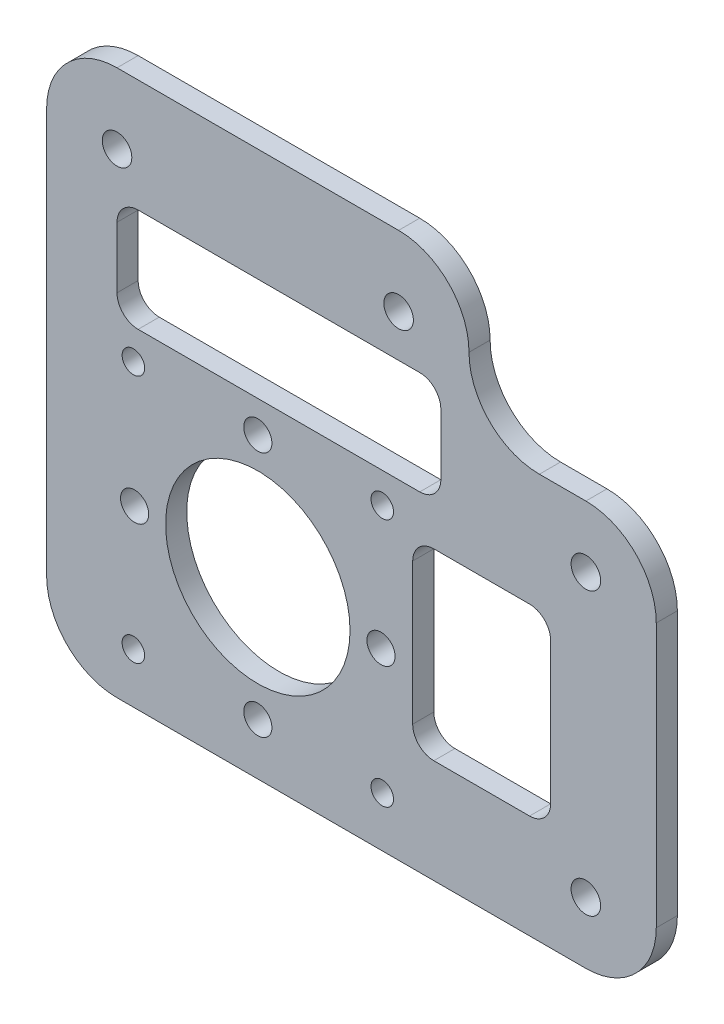
SolidWorks part; units mm, degrees
material "Thornel Mat VMA"
ref_plane "前视基准面" through (0, 0, 0) normal (0, 0, 1) x (1, 0, 0)
ref_plane "上视基准面" through (0, 0, 0) normal (0, 1, 0) x (1, 0, 0)
ref_plane "右视基准面" through (0, 0, 0) normal (1, 0, 0) x (0, 0, -1)
sketch "草图1" plane through (0, 0, 0) normal (0, 0, 1) x (1, 0, 0)
  line L0 (0, 0) -> (0, 77.5)
  line L1 (0, 77.5) -> (60, 77.5)
  line L2 (60, 77.5) -> (60, 57.5)
  line L3 (60, 57.5) -> (86.6, 57.5)
  line L4 (86.6, 57.5) -> (86.6, 0)
  line L5 (86.6, 0) -> (0, 0)
  line L12 (12.3223, 42.5) -> (30, 24.8223) construction
  line L13 (30, 24.8223) -> (47.6777, 42.5) construction
  line L14 (12.5, 24.8223) -> (30, 24.8223) construction
  line L15 (30, 24.8223) -> (30, 42.3223) construction
  circle A6 centre (12.3223, 42.5) radius 1.6
  circle A7 centre (30, 42.3223) radius 2
  circle A8 centre (30, 24.8223) radius 13.1
  circle A9 centre (12.5, 24.8223) radius 2
  circle A10 centre (12.3223, 7.1447) radius 1.6
  circle A11 centre (30, 7.3223) radius 2
  circle A12 centre (47.6777, 7.1447) radius 1.6
  circle A13 centre (47.5, 24.8223) radius 2
  circle A14 centre (47.6777, 42.5) radius 1.6
  circle A15 centre (30, 24.8223) radius 17.5 construction
  circle A16 centre (30, 24.8223) radius 25 construction
  point P8 (30, 7.1447)
  dimension "D1" = 35
  dimension "D2" = 26.2
  dimension "D3" = 4
  dimension "D4" = 4
  dimension "D5" = 4
  dimension "D6" = 4
  dimension "D7" = 3.2
  dimension "D8" = 3.2
  dimension "D9" = 3.2
  dimension "D10" = 3.2
  dimension "D11" = 50
  dimension "D12" = 35
  dimension "D13" = 77.5
  dimension "D14" = 20
  dimension "D15" = 30
  dimension "D16" = 60
  dimension "D17" = 90
  dimension "D18" = 26.6
extrude "凸台-拉伸1" add sketch "草图1" along normal blind 3
sketch "草图2" plane through (0, 0, 3) normal (0, 0, 1) x (1, 0, 0)
  line L0 (76.6, 57.5) -> (76.6, 0) construction
  line L1 (86.6, 57.5) -> (60, 57.5) construction
  line L2 (0, 0) -> (86.6, 0) construction
  line L3 (60, 67.5) -> (0, 67.5) construction
  line L4 (60, 57.5) -> (60, 77.5) construction
  line L5 (0, 77.5) -> (0, 0) construction
  line L6 (60, 77.5) -> (0, 77.5) construction
  line L7 (86.6, 0) -> (86.6, 57.5) construction
  line L8 (30, 77.5) -> (30, 61.9891) construction
  line L9 (86.6, 28.75) -> (68.6396, 28.75) construction
  circle A0 centre (10, 67.5) radius 2.1
  circle A1 centre (50, 67.5) radius 2.1
  circle A2 centre (76.6, 48.75) radius 2.1
  circle A3 centre (76.6, 8.75) radius 2.1
  dimension "D3" = 4.2
  dimension "D4" = 40
  dimension "D5" = 4.2
  dimension "D6" = 40
  dimension "D1" = 10
  dimension "D2" = 10
extrude "切除-拉伸1" cut sketch "草图2" against normal through all
fillet "圆角1" radius 10 6 edges at (0, 77.5, 1.5) (0, 0, 1.5) (86.6, 0, 1.5) (86.6, 57.5, 1.5) (60, 77.5, 1.5) (60, 57.5, 1.5)
sketch "草图4" plane through (0, 0, 3) normal (0, 0, 1) x (1, 0, 0)
  line L5 (52, 40.8223) -> (71.6, 40.8223)
  line L6 (52, 40.8223) -> (52, 14.75)
  line L7 (52, 14.75) -> (71.6, 14.75)
  line L8 (71.6, 40.8223) -> (71.6, 14.75)
  line L14 (10, 61.5) -> (10, 46.8223)
  line L15 (10, 46.8223) -> (56, 46.8223)
  line L16 (56, 46.8223) -> (56, 61.5)
  line L17 (56, 61.5) -> (10, 61.5)
  line L20 (0, 67.5) -> (0, 10) construction
  line L22 (86.6, 10) -> (86.6, 47.5) construction
  circle A3 centre (50, 67.5) radius 2.1 construction
  circle A5 centre (30, 24.8223) radius 13.1 construction
  circle A6 centre (76.6, 8.75) radius 2.1 construction
  point P0 (0, 0)
  dimension "D2" = 10
  dimension "D6" = 22
  dimension "D7" = 6
  dimension "D8" = 6
  dimension "D9" = 22
  dimension "D10" = 6
  dimension "D11" = 15
  dimension "D12" = 6
extrude "切除-拉伸2" cut sketch "草图4" against normal through all
fillet "圆角2" radius 3 8 edges at (71.6, 14.75, 1.5) (52, 14.75, 1.5) (71.6, 40.8223, 1.5) (52, 40.8223, 1.5) (56, 61.5, 1.5) (56, 46.8223, 1.5) (10, 46.8223, 1.5) (10, 61.5, 1.5)
